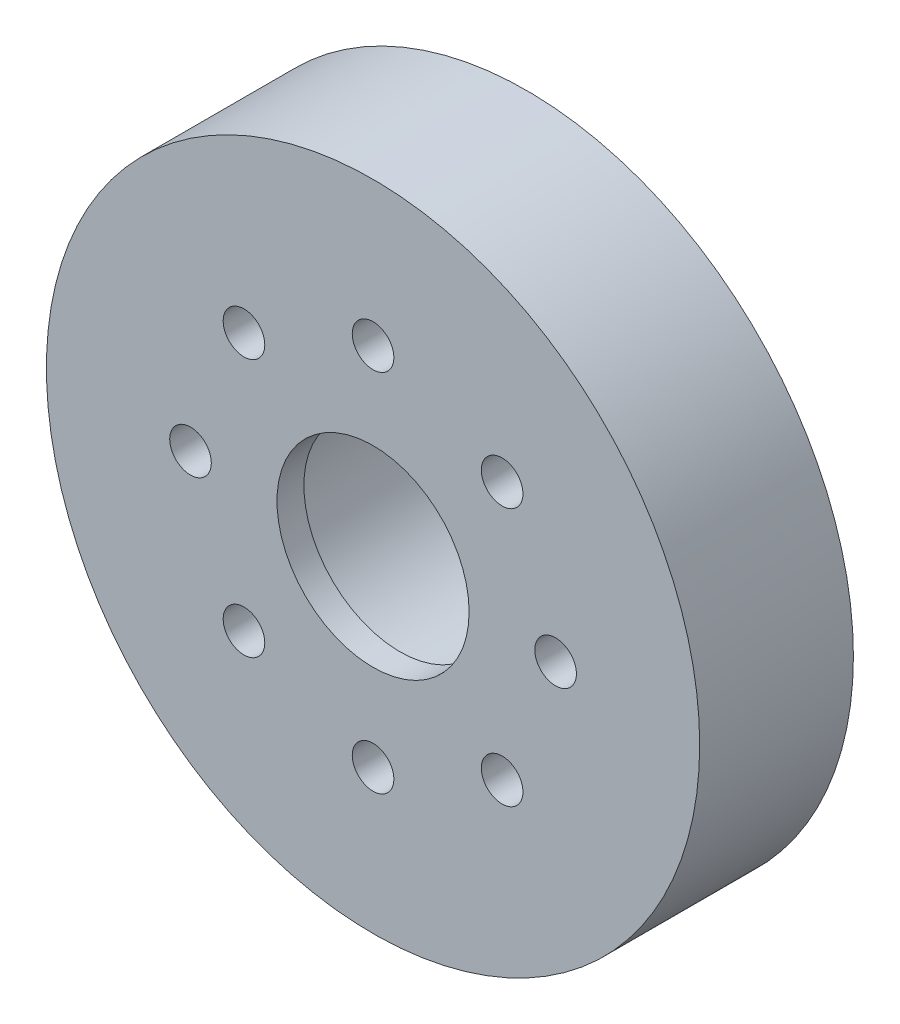
SolidWorks part; units mm, degrees
ref_plane "Front Plane" through (0, 0, 0) normal (0, 0, 1) x (1, 0, 0)
ref_plane "Top Plane" through (0, 0, 0) normal (0, 1, 0) x (1, 0, 0)
ref_plane "Right Plane" through (0, 0, 0) normal (1, 0, 0) x (0, 0, -1)
sketch "Sketch1" plane through (0, 0, 0) normal (0, 0, 1) x (1, 0, 0)
  circle A0 centre (0, 0) radius 43.18
  dimension "D1" = 86.36
extrude "Boss-Extrude1" add sketch "Sketch1" along normal blind 20.32
sketch "Sketch5" plane through (0, 0, 0) normal (0, 0, -1) x (-1, 0, 0)
  point P0 (0, 0)
sketch "Sketch6" plane through (0, 0, 0) normal (0, 0, -1) x (-1, 0, 0)
  circle A0 centre (0, 0) radius 29.21 construction
  circle A1 centre (0, 0) radius 24.13 construction
  point P5 (0, 24.13)
  dimension "D1" = 58.42
  dimension "D2" = 5.08
hole_wizard "1 NPT Tapped Hole2" positions "Sketch5" profile "Sketch7" size "1" standard "ANSI Inch" end condition up to next
sketch "Sketch7" plane through (0, 0, 0) normal (1, 0, 0) x (0, 1, 0)
  line L0 (0, 0) -> (0, 20.32)
  line L1 (0, 20.32) -> (14.4907, 20.32)
  line L2 (-15.228, 16.764) -> (-15.7299, 0) construction
  line L3 (14.4907, 20.32) -> (14.4907, 16.764)
  line L4 (14.4907, 16.764) -> (15.228, 16.764)
  line L5 (15.228, 16.764) -> (15.7299, 0)
  line L7 (15.7299, 0) -> (0, 0)
  line L8 (0, -6.35) -> (0, 107.95) construction
  line L11 (-14.4907, 16.764) -> (-15.228, 16.764) construction
  dimension "Thru Tap Drill Dia." = 28.9814
  dimension "Thru Tap Drill Depth" = 20.32
  dimension "Thread Dia." = 31.4598
  dimension "Thread Angle" = 3.43
  dimension "Thread Depth" = 16.764
cosmetic thread "Hole Thread1" parameters "D1"=16.764, "D2"=33.3988
hole_wizard "M5 Clearance Hole1" positions "Sketch6" profile "Sketch8" hole size "M5" standard "ANSI Metric" end condition up to next
sketch "Sketch8" plane through (0, 24.13, 0) normal (1, 0, 0) x (0, 1, 0)
  line L0 (0, 0) -> (0, 20.32)
  line L1 (0, 20.32) -> (2.75, 20.32)
  line L2 (2.75, 20.32) -> (2.75, 0)
  line L5 (2.75, 0) -> (0, 0)
  line L11 (0, -6.35) -> (0, 107.95) construction
  dimension "Thru Hole Dia." = 5.5
  dimension "Thru Hole Depth" = 20.32
pattern_circular "CirPattern1" count 8 every 45 about axis through (0, 0, 0) along (0, 0, -1) of "M5 Clearance Hole1"
sketch "Sketch9" plane through (0, 0, 20.32) normal (0, 0, 1) x (1, 0, 0)
  circle A0 centre (0, 0) radius 12.7
  circle A1 centre (0, 0) radius 14.4907 construction
  circle A2 centre (0, 0) radius 14.4907
  dimension "D1" = 25.4
extrude "Boss-Extrude2" add sketch "Sketch9" against normal up to surface (3.556 mm away) up to face at (-14.4907, 0, 16.764)
equation "\"cavity_depth\"=0.031in"
equation "\"Cavity_width\"=0.031in"
equation "\"tooth_width\"=0.01in"
equation "\"Flange_OD\"=2.3in"
equation "\"fitting_OD\"= 1.3in"
equation "\"plate_thick\"= .8in"
equation "\"D1@Boss-Extrude1\"=\"plate_thick\""
equation "\"D1@Sketch6\"=\"Flange_OD\""
equation "\"D1@Sketch1\"=\"IPS_flange_radius\"*2"
equation "\"bearing_radius\"= 0.629921"
equation "\"bearing_width\"=0.393701"
equation "\"kero_radius\"=0.334in"
equation "\"lox_radius\"=0.23622in"
equation "\"seal_step\"=0.01in"
equation "\"purge_length\"=0.04in"
equation "\"insert_radius\" = 0.6in"
equation "\"recycle_groove width\" = 0.06in"
equation "\"recycle_groove_depth\" = 0.06in"
equation "\"N2_purge_width\"= .06in"
equation "\"N2_purge_depth\"= .06in"
equation "\"drain_width\"= .06in"
equation "\"drain_depth\"= .06in"
equation "\"radial_clearance\"= .002in"
equation "\"IPS_flange_width\"= .4in"
equation "\"IPS_flange_radius\" = 1.7in"
equation "\"IPS_LOX_male_radius\"= .9in"
equation "\"IPS_Kero_male_radius\" = .9in"
equation "\"IPS_radius\"= 1.2in"
equation "\"InsertLength\"= 1in"
